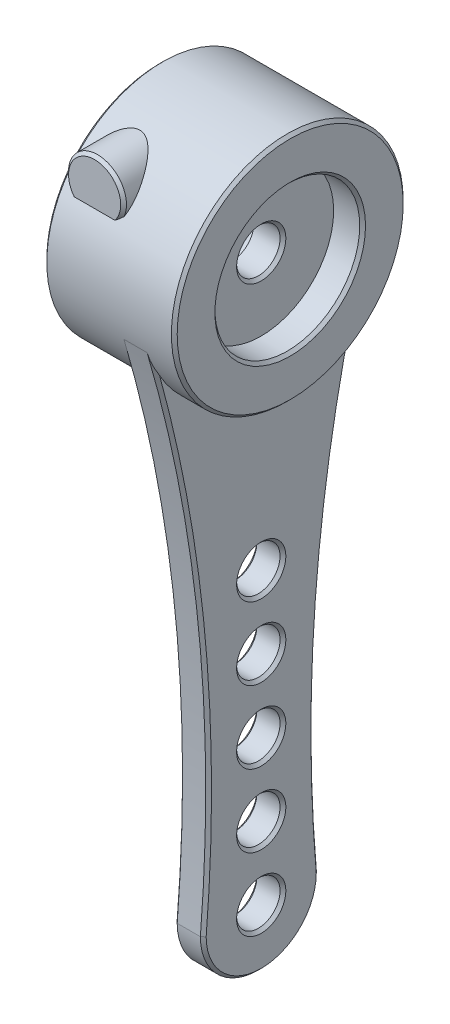
SolidWorks part; units mm, degrees
ref_plane "前视基准面" through (0, 0, 0) normal (0, 0, 1) x (1, 0, 0)
ref_plane "上视基准面" through (0, 0, 0) normal (0, 1, 0) x (1, 0, 0)
ref_plane "右视基准面" through (0, 0, 0) normal (1, 0, 0) x (0, 0, -1)
other "Configuration Table"
sketch "草图1" plane through (0, 0, 0) normal (1, 0, 0) x (0, 0, -1)
  line L0 (0, -160.1009) -> (0, 394.7407) construction
  arc A0 (-4, 0) -> (4, 0) centre (0, 0) ccw
  arc A1 (4, 0) -> (7.6763, 36.7474) centre (103.6304, 8.5903) cw
  circle A2 centre (0, 39) radius 8
  arc A3 (-4, 0) -> (-7.6763, 36.7474) centre (-103.6304, 8.5903) ccw
  circle A4 centre (0, 0) radius 1.5
  circle A5 centre (0, 5) radius 1.5
  circle A6 centre (0, 10) radius 1.5
  circle A7 centre (0, 15) radius 1.5
  circle A8 centre (0, 20) radius 1.5
  point P23 (-19.7955, 11.7405)
  dimension "D1" = 16
  dimension "D2" = 8
  dimension "D3" = 100
  dimension "D5" = 3
  dimension "D6" = 3
  dimension "D7" = 3
  dimension "D8" = 3
  dimension "D9" = 3
  dimension "D4" = 39
  dimension "D10" = 5
  dimension "D11" = 5
  dimension "D12" = 5
  dimension "D13" = 5
extrude "凸台-拉伸1" add sketch "草图1" along normal blind 2 contours A0 L0 A4 A5 A6 A7 A8 A2 A3 | L0 A0 A1 A2 A8 A7 A6 A5 A4 region at (0, 16.7924, 2.5122) region at (0, 16.7924, -2.5122)
sketch "草图2" plane through (0, 0, 0) normal (1, 0, 0) x (0, 0, -1)
  line L0 (0, 0) -> (0, 62.0355)
  circle A0 centre (0, 39) radius 8
  arc A1 (-7.6763, 36.7474) -> (7.6763, 36.7474) centre (0, 39) ccw construction
  dimension "D1" = 16
extrude "凸台-拉伸2" add sketch "草图2" along normal blind 4 and the other way blind 5 contours L0 A0 | L0 A0 region at (0, 39, 3.3953) region at (0, 39, -3.3953)
sketch "草图3" plane through (4, 0, 0) normal (1, 0, 0) x (0, 0, -1)
  circle A0 centre (0, 39) radius 5
  circle A1 centre (0, 39) radius 8 construction
  dimension "D1" = 10
extrude "切除-拉伸1" cut sketch "草图3" against normal blind 2 contours A0
sketch "草图4" plane through (2, 0, 0) normal (1, 0, 0) x (0, 0, -1)
  circle A0 centre (0, 39) radius 1.5
  circle A1 centre (0, 39) radius 5 construction
  dimension "D1" = 3
extrude "切除-拉伸2" cut sketch "草图4" against normal blind 2 contours A0
sketch "草图5" plane through (-5, 0, 0) normal (-1, 0, 0) x (0, 0, 1)
  circle A0 centre (0, 39) radius 3
  circle A1 centre (0, 39) radius 8 construction
  dimension "D1" = 6
extrude "切除-拉伸3" cut sketch "草图5" against normal blind 5 contours A0
ref_plane "基准面1" through (0, 0, 7) normal (0, 0, 1) x (1, 0, 0)
sketch "草图7" plane through (0, 0, 7) normal (0, 0, 1) x (1, 0, 0)
  line L1 (0, 36.7474) -> (0, 31) construction
  line L2 (-5, 47) -> (-5, 31) construction
  line L3 (-4.0059, 42.6838) -> (-0.9941, 42.6838)
  arc A0 (-4.0059, 42.6838) -> (-0.9941, 42.6838) centre (-2.5, 44) cw
  point P5 (-5, 39)
  dimension "D3" = 2
  dimension "D1" = 2.5
  dimension "D2" = 5
extrude "凸台-拉伸3" add sketch "草图7" against normal up to surface (14.1014 mm away) contours L3 A0 up to face at (4, 39, -8)
chamfer "倒角1" distance 0.2 angle 45 5 edges at (-5, 39, 3) (-5, 39, -8) (-2.5, 46, 7) (4, 39, -5) (4, 39, -8)
chamfer "倒角2" distance 0.2 angle 45 10 edges at (0, 0, -1.5) (0, 5, -1.5) (0, 10, -1.5) (0, 15, -1.5) (0, 20, -1.5) (2, 0, -1.5) (2, 5, -1.5) (2, 10, -1.5) (2, 15, -1.5) (2, 20, -1.5)
chamfer "倒角3" distance 0.2 angle 45 4 edges at (0, 18.5449, -4.1271) (0, 18.5449, 4.1271) (2, 18.5449, -4.1271) (2, 18.5449, 4.1271)
chamfer "倒角4" distance 0.2 angle 45 2 edges at (2, -4, 0) (0, -4, 0)
chamfer "倒角5" distance 0.2 angle 45 1 edges at (2, 39, -1.5)
